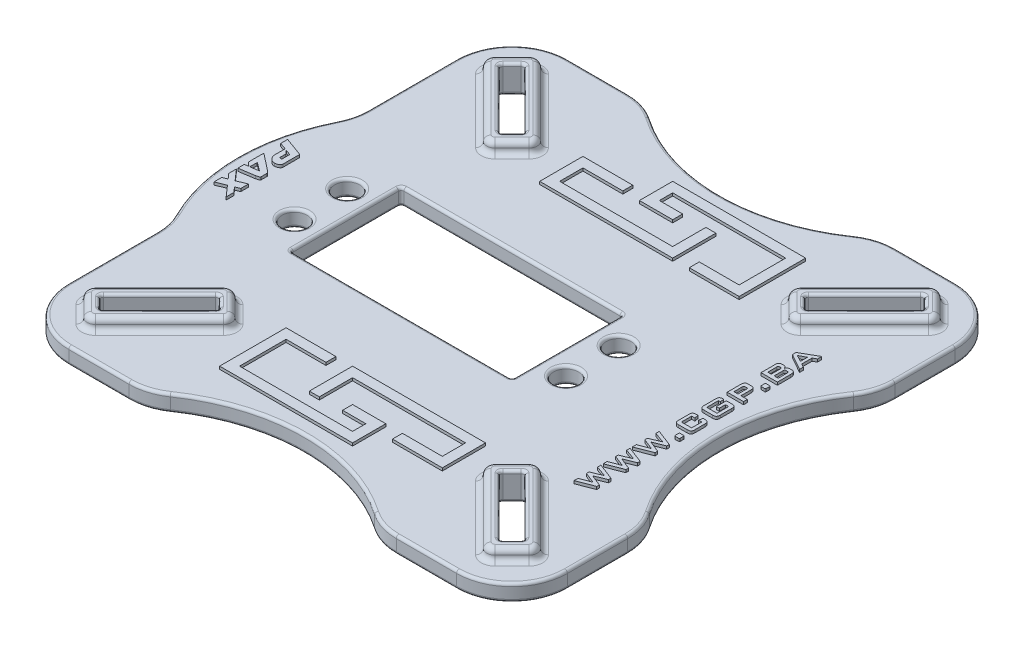
SolidWorks part; units mm, degrees
ref_plane "Front Plane" through (0, 0, 0) normal (0, 0, 1) x (1, 0, 0)
ref_plane "Top Plane" through (0, 0, 0) normal (0, 1, 0) x (1, 0, 0)
ref_plane "Right Plane" through (0, 0, 0) normal (1, 0, 0) x (0, 0, -1)
sketch "Sketch1" plane through (0, 0, 0) normal (0, 1, 0) x (1, 0, 0)
  line L1 (-45, 45) -> (45, 45)
  line L2 (-45, 45) -> (-45, -45)
  line L3 (-45, -45) -> (45, -45)
  line L4 (45, 45) -> (45, -45)
  line L5 (-45, 45) -> (45, -45) construction
  line L6 (-45, -45) -> (45, 45) construction
  line L7 (-30, 10) -> (10, 10)
  line L8 (-30, 10) -> (-30, -10)
  line L9 (-30, -10) -> (10, -10)
  line L10 (10, 10) -> (10, -10)
  circle A0 centre (0, 0) radius 10 construction
  point P0 (0, 0)
  point P5 (0, 0)
  dimension "D4" = 20
  dimension "D1" = 90
  dimension "D2" = 20
  dimension "D3" = 40
extrude "Boss-Extrude1" add sketch "Sketch1" along normal blind 3
sketch "Sketch2" plane through (0, 3, 0) normal (0, 1, 0) x (1, 0, 0)
  line L0 (-30, 10) -> (10, -10) construction
  line L1 (-34.5, 4.75) -> (14.5, 4.75) construction
  line L2 (-34.5, 4.75) -> (-34.5, -4.75) construction
  line L3 (-34.5, -4.75) -> (14.5, -4.75) construction
  line L4 (14.5, 4.75) -> (14.5, -4.75) construction
  line L5 (-34.5, 4.75) -> (14.5, -4.75) construction
  line L6 (-34.5, -4.75) -> (14.5, 4.75) construction
  circle A0 centre (-34.5, 4.75) radius 2.25
  circle A1 centre (-34.5, -4.75) radius 2.25
  circle A2 centre (14.5, 4.75) radius 2.25
  circle A3 centre (14.5, -4.75) radius 2.25
  point P0 (-10, 0)
  dimension "D3" = 4.5
  dimension "D4" = 4.5
  dimension "D5" = 4.5
  dimension "D6" = 4.5
  dimension "D1" = 9.5
  dimension "D2" = 49
extrude "Cut-Extrude1" cut sketch "Sketch2" against normal blind 3
sketch "Sketch3" plane through (0, 3, 0) normal (0, 1, 0) x (1, 0, 0)
  circle A0 centre (0, 70) radius 32.5
  circle A1 centre (0, 0) radius 6.12 construction
  circle A2 centre (70, 0) radius 32.5
  circle A3 centre (0, -70) radius 32.5
  point P13 (0, 0)
  dimension "D1" = 65
  dimension "D2" = 70
extrude "Cut-Extrude2" cut sketch "Sketch3" against normal blind 3
fillet "Fillet1" radius 10 4 edges at (-45, 1.5, -45) (45, 1.5, -45) (-45, 1.5, 45) (45, 1.5, 45)
fillet "Fillet2" radius 10 2 edges at (45, 1.5, 20.7666) (45, 1.5, -20.7666)
sketch "Sketch4" plane through (0, 3, 0) normal (0, 1, 0) x (1, 0, 0)
  line L0 (0, 0) -> (-42.0711, 42.0711) construction
  line L1 (-38.3959, 36.0624) -> (-27.5772, 25.2437)
  line L2 (-38.3959, 36.0624) -> (-36.0624, 38.3959)
  line L3 (-27.5772, 25.2437) -> (-25.2437, 27.5772)
  line L4 (-36.0624, 38.3959) -> (-25.2437, 27.5772)
  line L5 (-38.3959, 36.0624) -> (-25.2437, 27.5772) construction
  line L6 (-27.5772, 25.2437) -> (-36.0624, 38.3959) construction
  line L7 (36.0624, 38.3959) -> (25.2437, 27.5772)
  line L8 (36.0624, 38.3959) -> (38.3959, 36.0624)
  line L9 (25.2437, 27.5772) -> (27.5772, 25.2437)
  line L10 (38.3959, 36.0624) -> (27.5772, 25.2437)
  line L11 (0, 0) -> (42.0711, 42.0711) construction
  line L12 (36.0624, 38.3959) -> (27.5772, 25.2437) construction
  line L13 (25.2437, 27.5772) -> (38.3959, 36.0624) construction
  line L14 (38.3959, -36.0624) -> (27.5772, -25.2437)
  line L15 (38.3959, -36.0624) -> (36.0624, -38.3959)
  line L16 (27.5772, -25.2437) -> (25.2437, -27.5772)
  line L17 (36.0624, -38.3959) -> (25.2437, -27.5772)
  line L18 (0, 0) -> (42.0711, -42.0711) construction
  line L19 (38.3959, -36.0624) -> (25.2437, -27.5772) construction
  line L20 (27.5772, -25.2437) -> (36.0624, -38.3959) construction
  line L21 (-36.0624, -38.3959) -> (-25.2437, -27.5772)
  line L22 (-36.0624, -38.3959) -> (-38.3959, -36.0624)
  line L23 (-25.2437, -27.5772) -> (-27.5772, -25.2437)
  line L24 (-38.3959, -36.0624) -> (-27.5772, -25.2437)
  line L25 (0, 0) -> (-42.0711, -42.0711) construction
  line L26 (-36.0624, -38.3959) -> (-27.5772, -25.2437) construction
  line L27 (-25.2437, -27.5772) -> (-38.3959, -36.0624) construction
  arc A0 (-35, 45) -> (-45, 35) centre (-35, 35) ccw construction
  circle A1 centre (0, 0) radius 6.1388 construction
  point P7 (-31.8198, 31.8198)
  point P11 (31.8198, 31.8198)
  point P21 (31.8198, -31.8198)
  point P27 (-31.8198, -31.8198)
  point P32 (0, 0)
  dimension "D4" = 4
  dimension "D1" = 15.3
  dimension "D2" = 45
  dimension "D3" = 3.3
extrude "Cut-Extrude3" cut sketch "Sketch4" against normal blind 3
fillet "Fillet3" radius 10 4 edges at (20.7666, 1.5, -45) (-20.7666, 1.5, -45) (-20.7666, 1.5, 45) (20.7666, 1.5, 45)
sketch "Sketch5" plane through (0, 3, 0) normal (0, 1, 0) x (1, 0, 0)
  line L0 (-5.8042, -22.9756) -> (-5.8042, -30.7756)
  line L1 (-5.8042, -30.7756) -> (-4.0042, -30.7756)
  line L2 (-4.0042, -30.7756) -> (-4.0042, -24.7756)
  line L3 (-4.0042, -24.7756) -> (16.3958, -24.7756)
  line L4 (16.3958, -24.7756) -> (16.3958, -28.9756)
  line L5 (16.3958, -28.9756) -> (9.1958, -28.9756)
  line L6 (9.1958, -28.9756) -> (9.1958, -30.7756)
  line L7 (9.1958, -30.7756) -> (18.1958, -30.7756)
  line L8 (18.1958, -30.7756) -> (18.1958, -22.9756)
  line L9 (18.1958, -22.9756) -> (-5.8042, -22.9756)
  line L10 (-17.8042, -22.9756) -> (-17.8042, -34.9756)
  line L11 (-17.8042, -34.9756) -> (6.1958, -34.9756)
  line L12 (6.1958, -34.9756) -> (6.1958, -28.9756)
  line L13 (6.1958, -28.9756) -> (0.1958, -28.9756)
  line L14 (0.1958, -28.9756) -> (0.1958, -30.7756)
  line L15 (0.1958, -30.7756) -> (4.3958, -30.7756)
  line L16 (4.3958, -30.7756) -> (4.3958, -33.1756)
  line L17 (4.3958, -33.1756) -> (-16.0042, -33.1756)
  line L18 (-16.0042, -33.1756) -> (-16.0042, -24.7756)
  line L19 (-16.0042, -24.7756) -> (-8.8042, -24.7756)
  line L20 (-8.8042, -24.7756) -> (-8.8042, -22.9756)
  line L21 (-8.8042, -22.9756) -> (-17.8042, -22.9756)
  line L22 (6.1958, 22.805) -> (6.1958, 30.605)
  line L23 (6.1958, 30.605) -> (4.3958, 30.605)
  line L24 (4.3958, 30.605) -> (4.3958, 24.605)
  line L25 (4.3958, 24.605) -> (-16.0042, 24.605)
  line L26 (-16.0042, 24.605) -> (-16.0042, 28.805)
  line L27 (-16.0042, 28.805) -> (-8.8042, 28.805)
  line L28 (-8.8042, 28.805) -> (-8.8042, 30.605)
  line L29 (-8.8042, 30.605) -> (-17.8042, 30.605)
  line L30 (-17.8042, 30.605) -> (-17.8042, 22.805)
  line L31 (-17.8042, 22.805) -> (6.1958, 22.805)
  line L32 (18.1958, 22.805) -> (18.1958, 34.805)
  line L33 (18.1958, 34.805) -> (-5.8042, 34.805)
  line L34 (-5.8042, 34.805) -> (-5.8042, 28.805)
  line L35 (-5.8042, 28.805) -> (0.1958, 28.805)
  line L36 (0.1958, 28.805) -> (0.1958, 30.605)
  line L37 (0.1958, 30.605) -> (-4.0042, 30.605)
  line L38 (-4.0042, 30.605) -> (-4.0042, 33.005)
  line L39 (-4.0042, 33.005) -> (16.3958, 33.005)
  line L40 (16.3958, 33.005) -> (16.3958, 24.605)
  line L41 (16.3958, 24.605) -> (9.1958, 24.605)
  line L42 (9.1958, 24.605) -> (9.1958, 22.805)
  line L43 (9.1958, 22.805) -> (18.1958, 22.805)
extrude "Boss-Extrude2" add sketch "Sketch5" along normal blind 0.5
sketch "Sketch6" plane through (0, 3, 0) normal (0, 1, 0) x (1, 0, 0)
  line L0 (-27.5772, 25.2437) -> (-25.2437, 27.5772) construction
  line L1 (-38.3959, 36.0624) -> (-27.5772, 25.2437) construction
  line L2 (-36.0624, 38.3959) -> (-38.3959, 36.0624) construction
  line L3 (-25.2437, 27.5772) -> (-36.0624, 38.3959) construction
  line L4 (-27.5772, 25.2437) -> (-25.2437, 27.5772)
  line L5 (-38.3959, 36.0624) -> (-27.5772, 25.2437)
  line L6 (-36.0624, 38.3959) -> (-38.3959, 36.0624)
  line L7 (-25.2437, 27.5772) -> (-36.0624, 38.3959)
  line L8 (-26.5165, 23.4759) -> (-23.4759, 26.5165)
  line L9 (-23.4759, 28.6378) -> (-35.0018, 40.1637)
  line L10 (-37.1231, 40.1637) -> (-40.1637, 37.1231)
  line L11 (-40.1637, 35.0018) -> (-28.6378, 23.4759)
  line L12 (-36.0624, 41.2243) -> (-41.2243, 36.0624) construction
  line L13 (-41.2243, 36.0624) -> (-27.5772, 22.4153) construction
  line L14 (-22.4153, 27.5772) -> (-36.0624, 41.2243) construction
  line L15 (-27.5772, 22.4153) -> (-22.4153, 27.5772) construction
  line L16 (25.2437, 27.5772) -> (27.5772, 25.2437)
  line L17 (36.0624, 38.3959) -> (25.2437, 27.5772)
  line L18 (38.3959, 36.0624) -> (36.0624, 38.3959)
  line L19 (27.5772, 25.2437) -> (38.3959, 36.0624)
  line L20 (23.4759, 26.5165) -> (26.5165, 23.4759)
  line L21 (28.6378, 23.4759) -> (40.1637, 35.0018)
  line L22 (40.1637, 37.1231) -> (37.1231, 40.1637)
  line L23 (35.0018, 40.1637) -> (23.4759, 28.6378)
  line L24 (27.5772, -25.2437) -> (25.2437, -27.5772)
  line L25 (38.3959, -36.0624) -> (27.5772, -25.2437)
  line L26 (36.0624, -38.3959) -> (38.3959, -36.0624)
  line L27 (25.2437, -27.5772) -> (36.0624, -38.3959)
  line L28 (26.5165, -23.4759) -> (23.4759, -26.5165)
  line L29 (23.4759, -28.6378) -> (35.0018, -40.1637)
  line L30 (37.1231, -40.1637) -> (40.1637, -37.1231)
  line L31 (40.1637, -35.0018) -> (28.6378, -23.4759)
  line L32 (-25.2437, -27.5772) -> (-27.5772, -25.2437)
  line L33 (-36.0624, -38.3959) -> (-25.2437, -27.5772)
  line L34 (-38.3959, -36.0624) -> (-36.0624, -38.3959)
  line L35 (-27.5772, -25.2437) -> (-38.3959, -36.0624)
  line L36 (-23.4759, -26.5165) -> (-26.5165, -23.4759)
  line L37 (-28.6378, -23.4759) -> (-40.1637, -35.0018)
  line L38 (-40.1637, -37.1231) -> (-37.1231, -40.1637)
  line L39 (-35.0018, -40.1637) -> (-23.4759, -28.6378)
  circle A0 centre (0, 0) radius 4.6074 construction
  arc A1 (-40.1637, 37.1231) -> (-40.1637, 35.0018) centre (-39.103, 36.0624) ccw
  arc A2 (-35.0018, 40.1637) -> (-37.1231, 40.1637) centre (-36.0624, 39.103) ccw
  arc A3 (-23.4759, 26.5165) -> (-23.4759, 28.6378) centre (-24.5366, 27.5772) ccw
  arc A4 (-26.5165, 23.4759) -> (-28.6378, 23.4759) centre (-27.5772, 24.5366) cw
  arc A5 (37.1231, 40.1637) -> (35.0018, 40.1637) centre (36.0624, 39.103) ccw
  arc A6 (40.1637, 35.0018) -> (40.1637, 37.1231) centre (39.103, 36.0624) ccw
  arc A7 (26.5165, 23.4759) -> (28.6378, 23.4759) centre (27.5772, 24.5366) ccw
  arc A8 (23.4759, 26.5165) -> (23.4759, 28.6378) centre (24.5366, 27.5772) cw
  arc A9 (40.1637, -37.1231) -> (40.1637, -35.0018) centre (39.103, -36.0624) ccw
  arc A10 (35.0018, -40.1637) -> (37.1231, -40.1637) centre (36.0624, -39.103) ccw
  arc A11 (23.4759, -26.5165) -> (23.4759, -28.6378) centre (24.5366, -27.5772) ccw
  arc A12 (26.5165, -23.4759) -> (28.6378, -23.4759) centre (27.5772, -24.5366) cw
  arc A13 (-37.1231, -40.1637) -> (-35.0018, -40.1637) centre (-36.0624, -39.103) ccw
  arc A14 (-40.1637, -35.0018) -> (-40.1637, -37.1231) centre (-39.103, -36.0624) ccw
  arc A15 (-26.5165, -23.4759) -> (-28.6378, -23.4759) centre (-27.5772, -24.5366) ccw
  arc A16 (-23.4759, -26.5165) -> (-23.4759, -28.6378) centre (-24.5366, -27.5772) cw
  point P74 (0.1061, -0.1061)
  point P75 (0, 0)
  dimension "D2" = 1.5
  dimension "D1" = 2
  dimension "D3" = 4
extrude "Boss-Extrude3" add sketch "Sketch6" along normal blind 2
fillet "Fillet4" radius 1 64 edges at (-27.5772, 3, -23.0366) (-34.4007, 3, -29.2389) (-40.603, 3, -36.0624) (-38.6434, 3, -38.6434) (-36.0624, 3, -40.603) (-29.2389, 3, -34.4007) (-23.0366, 3, -27.5772) (-27.5772, 5, -23.0366) (-34.4007, 5, -29.2389) (-40.603, 5, -36.0624) (-38.6434, 5, -38.6434) (-36.0624, 5, -40.603) (-29.2389, 5, -34.4007) (-23.0366, 5, -27.5772) (-24.9962, 3, -24.9962) (-24.9962, 5, -24.9962) (27.5772, 5, -23.0366) (24.9962, 5, -24.9962) (23.0366, 5, -27.5772) (29.2389, 5, -34.4007) (36.0624, 5, -40.603) (38.6434, 5, -38.6434) (40.603, 5, -36.0624) (27.5772, 3, -23.0366) (24.9962, 3, -24.9962) (23.0366, 3, -27.5772) (29.2389, 3, -34.4007) (36.0624, 3, -40.603) (38.6434, 3, -38.6434) (40.603, 3, -36.0624) (36.0624, 5, 40.603) (29.2389, 5, 34.4007) (23.0366, 5, 27.5772) (24.9962, 5, 24.9962) (27.5772, 5, 23.0366) (34.4007, 5, 29.2389) (40.603, 5, 36.0624) (36.0624, 3, 40.603) (29.2389, 3, 34.4007) (23.0366, 3, 27.5772) (24.9962, 3, 24.9962) (27.5772, 3, 23.0366) (34.4007, 3, 29.2389) (40.603, 3, 36.0624) (-36.0624, 3, 40.603) (-38.6434, 3, 38.6434) (-40.603, 3, 36.0624) (-34.4007, 3, 29.2389) (-27.5772, 3, 23.0366) (-24.9962, 3, 24.9962) (-23.0366, 3, 27.5772) (-27.5772, 5, 23.0366) (-24.9962, 5, 24.9962) (-23.0366, 5, 27.5772) (-29.2389, 5, 34.4007) (-36.0624, 5, 40.603) (-38.6434, 5, 38.6434) (-40.603, 5, 36.0624) (34.4007, 5, -29.2389) (34.4007, 3, -29.2389) (38.6434, 5, 38.6434) (38.6434, 3, 38.6434) (-29.2389, 3, 34.4007) (-34.4007, 5, 29.2389)
sketch "Sketch7" plane through (0, 3, 0) normal (0, 1, 0) x (1, 0, 0)
  line L0 (45, 24.1091) -> (45, 35) construction
  line L1 (-41.2733, 21.6115) -> (-41.2733, -21.6115)
  arc A0 (-41.2733, 21.6115) -> (-41.2733, -21.6115) centre (-17, 0) ccw
  dimension "D1" = 65
  dimension "D2" = 62
extrude "Boss-Extrude4" add sketch "Sketch7" against normal blind 3 contours A0 L1
fillet "Fillet5" radius 10 2 edges at (-45, 1.5, 16.5) (-45, 1.5, -16.5)
sketch "Sketch8" plane through (0, 3, 0) normal (0, 1, 0) x (1, 0, 0)
  line L0 (-47.1089, 19.0329) -> (-47.1089, -19.0329) construction
  text T0 "pax" font "Airstrike" height in points 13
extrude "Boss-Extrude5" add sketch "Sketch8" along normal blind 0.5
sketch "Sketch9" plane through (0, 3, 0) normal (0, 1, 0) x (1, 0, 0)
  line L0 (35.03, 28.4539) -> (35.03, -28.4539) construction
  line L1 (40.8708, 34.2947) -> (29.3449, 22.7688) construction
  line L2 (29.3449, -22.7688) -> (40.8708, -34.2947) construction
  text T0 "WWW.CGP.BA" font "BankGothic Md BT" height in points 11
extrude "Boss-Extrude6" add sketch "Sketch9" along normal blind 0.5
fillet "Fillet6" radius 0.5 116 edges at (-45.2683, 0, 16.732) (-49.5, 0, 0) (-45.2683, 0, -16.732) (-45, 0, -27.0164) (-42.0711, 0, -42.0711) (-29.5546, 0, -45) (-21.1387, 0, -44.5486) (0, 0, -37.5) (21.1387, 0, -44.5486) (29.5546, 0, -45) (42.0711, 0, -42.0711) (45, 0, -29.5546) (44.5486, 0, -21.1387) (37.5, 0, 0) (44.5486, 0, 21.1387) (45, 0, 29.5546) (42.0711, 0, 42.0711) (29.5546, 0, 45) (21.1387, 0, 44.5486) (0, 0, 37.5) (-21.1387, 0, 44.5486) (-29.5546, 0, 45) (-42.0711, 0, 42.0711) (-45.2683, 3, 16.732) (-49.5, 3, 0) (-45.2683, 3, -16.732) (-45, 3, -27.0164) (-42.0711, 3, -42.0711) (-29.5546, 3, -45) (-21.1387, 3, -44.5486) (0, 3, -37.5) (21.1387, 3, -44.5486) (29.5546, 3, -45) (42.0711, 3, -42.0711) (45, 3, -29.5546) (44.5486, 3, -21.1387) (37.5, 3, 0) (44.5486, 3, 21.1387) (45, 3, 29.5546) (42.0711, 3, 42.0711) (29.5546, 3, 45) (21.1387, 3, 44.5486) (0, 3, 37.5) (-21.1387, 3, 44.5486) (-29.5546, 3, 45) (-42.0711, 3, 42.0711) (32.9865, 0, -30.6531) (32.9865, 5, -30.6531) (37.2292, 0, -37.2292) (37.2292, 5, -37.2292) (38.3959, 2.5, -36.0624) (30.6531, 0, -32.9865) (30.6531, 5, -32.9865) (36.0624, 2.5, -38.3959) (26.4104, 0, -26.4104) (27.5772, 2.5, -25.2437) (26.4104, 5, -26.4104) (25.2437, 2.5, -27.5772) (-37.2292, 0, 37.2292) (-37.2292, 5, 37.2292) (-30.6531, 0, 32.9865) (-30.6531, 5, 32.9865) (-36.0624, 2.5, 38.3959) (-26.4104, 0, 26.4104) (-26.4104, 5, 26.4104) (-25.2437, 2.5, 27.5772) (-32.9865, 0, 30.6531) (-38.3959, 2.5, 36.0624) (-32.9865, 5, 30.6531) (-27.5772, 2.5, 25.2437) (30.6531, 0, 32.9865) (30.6531, 5, 32.9865) (26.4104, 0, 26.4104) (25.2437, 2.5, 27.5772) (26.4104, 5, 26.4104) (32.9865, 0, 30.6531) (27.5772, 2.5, 25.2437) (32.9865, 5, 30.6531) (37.2292, 0, 37.2292) (38.3959, 2.5, 36.0624) (37.2292, 5, 37.2292) (36.0624, 2.5, 38.3959) (-26.4104, 0, -26.4104) (-26.4104, 5, -26.4104) (-30.6531, 0, -32.9865) (-30.6531, 5, -32.9865) (-25.2437, 2.5, -27.5772) (-37.2292, 0, -37.2292) (-37.2292, 5, -37.2292) (-36.0624, 2.5, -38.3959) (-32.9865, 0, -30.6531) (-27.5772, 2.5, -25.2437) (-32.9865, 5, -30.6531) (-38.3959, 2.5, -36.0624) (14.5, 3, -2.5) (14.5, 0, -2.5) (14.5, 3, 7) (14.5, 0, 7) (-34.5, 3, -2.5) (-34.5, 0, -2.5) (-34.5, 3, 7) (-34.5, 0, 7) (-10, 3, 10) (-10, 0, 10) (10, 3, 0) (10, 1.5, 10) (10, 0, 0) (-10, 3, -10) (10, 1.5, -10) (-10, 0, -10) (-30, 1.5, 10) (-30, 3, 0) (-30, 1.5, -10) (-30, 0, 0) (-45, 0, 27.0164) (-45, 3, 27.0164)
